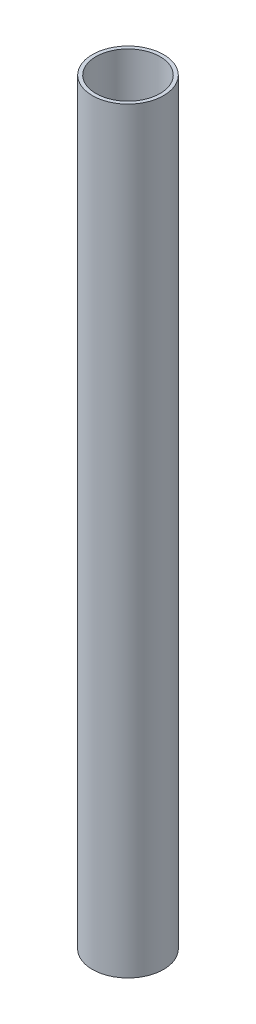
SolidWorks part; units mm, degrees
other "Boss-Extrude"
material "Toray T700"
ref_plane "Front" through (0, 0, 0) normal (0, 0, 1) x (1, 0, 0)
ref_plane "Top" through (0, 0, 0) normal (0, 1, 0) x (1, 0, 0)
ref_plane "Right" through (0, 0, 0) normal (1, 0, 0) x (0, 0, -1)
sketch "Sketch1" plane through (0, 0, 0) normal (0, 1, 0) x (1, 0, 0)
  line L5 (4.7969, 0) -> (-5.97, 0) construction
  circle A0 centre (0, 0) radius 10
  circle A1 centre (0, 0) radius 9
  dimension "D1" = 20
  dimension "D2" = 18
extrude "Boss-Extrude1" add sketch "Sketch1" along normal blind 212.6
ref_axis "Axis1" through (0, 0, 50) along (0, 0, -1)
